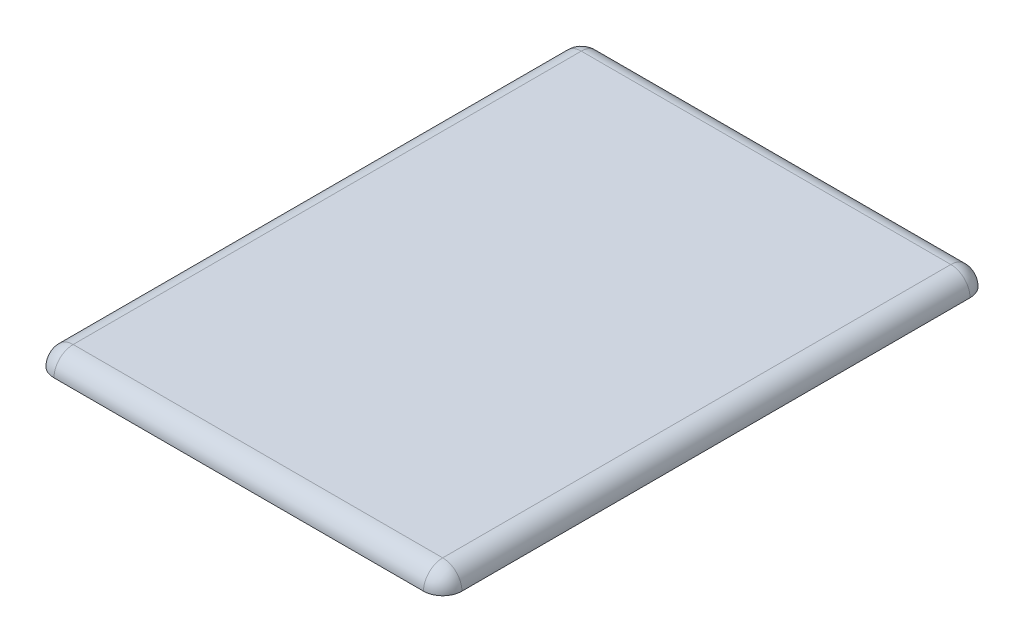
SolidWorks part; units mm, degrees
ref_plane "Front Plane" through (0, 0, 0) normal (0, 0, 1) x (1, 0, 0)
ref_plane "Top Plane" through (0, 0, 0) normal (0, 1, 0) x (1, 0, 0)
ref_plane "Right Plane" through (0, 0, 0) normal (1, 0, 0) x (0, 0, -1)
sketch "Sketch1" plane through (0, 0, 0) normal (0, 1, 0) x (1, 0, 0)
  line L1 (-53, -71) -> (53, -71)
  line L2 (-53, -71) -> (-53, 71)
  line L3 (-53, 71) -> (53, 71)
  line L4 (53, -71) -> (53, 71)
  line L5 (-53, -71) -> (53, 71) construction
  line L6 (-53, 71) -> (53, -71) construction
  point P0 (0, 0)
  dimension "D1" = 106
  dimension "D2" = 142
extrude "Boss-Extrude1" add sketch "Sketch1" along normal blind 5
sketch "Sketch2" plane through (0, 0, 0) normal (0, -1, 0) x (1, 0, 0)
  line L0 (53, 71) -> (53, -71) construction
  line L1 (-45, -63) -> (45, -63)
  line L2 (-45, -63) -> (-45, 63)
  line L3 (-45, 63) -> (45, 63)
  line L4 (45, -63) -> (45, 63)
  line L5 (-45, -63) -> (45, 63) construction
  line L6 (-45, 63) -> (45, -63) construction
  line L7 (53, -71) -> (-53, -71) construction
  point P0 (0, 0)
  dimension "D1" = 8
  dimension "D2" = 8
extrude "Boss-Extrude2" add sketch "Sketch2" along normal blind 5
sketch "Sketch3" plane through (0, -5, 0) normal (0, -1, 0) x (1, 0, 0)
  line L0 (45, -63) -> (45, 63) construction
  line L1 (-40, -58) -> (40, -58)
  line L2 (-40, -58) -> (-40, 58)
  line L3 (-40, 58) -> (40, 58)
  line L4 (40, -58) -> (40, 58)
  line L5 (-40, -58) -> (40, 58) construction
  line L6 (-40, 58) -> (40, -58) construction
  line L7 (-45, -63) -> (45, -63) construction
  point P0 (0, 0)
  dimension "D1" = 5
  dimension "D2" = 5
extrude "Cut-Extrude1" cut sketch "Sketch3" against normal blind 5
sketch "Sketch4" plane through (45, 0, 0) normal (1, 0, 0) x (0, 0, -1)
  line L0 (-63, -2.5) -> (63, -2.5) construction
  line L1 (-63, -5) -> (-63, 0) construction
  line L2 (63, -5) -> (63, 0) construction
  line L3 (63, 0) -> (-63, 0) construction
  line L4 (-12.5, -5) -> (12.5, -5)
  line L5 (-12.5, -5) -> (-12.5, 0)
  line L6 (-12.5, 0) -> (12.5, 0)
  line L7 (12.5, -5) -> (12.5, 0)
  line L8 (-12.5, -5) -> (12.5, 0) construction
  line L9 (-12.5, 0) -> (12.5, -5) construction
  point P6 (0, -2.5)
  dimension "D1" = 25
extrude "Cut-Extrude2" cut sketch "Sketch4" against normal blind 5
fillet "Fillet1" radius 5 4 edges at (0, 5, 71) (-53, 5, 0) (0, 5, -71) (53, 5, 0)
